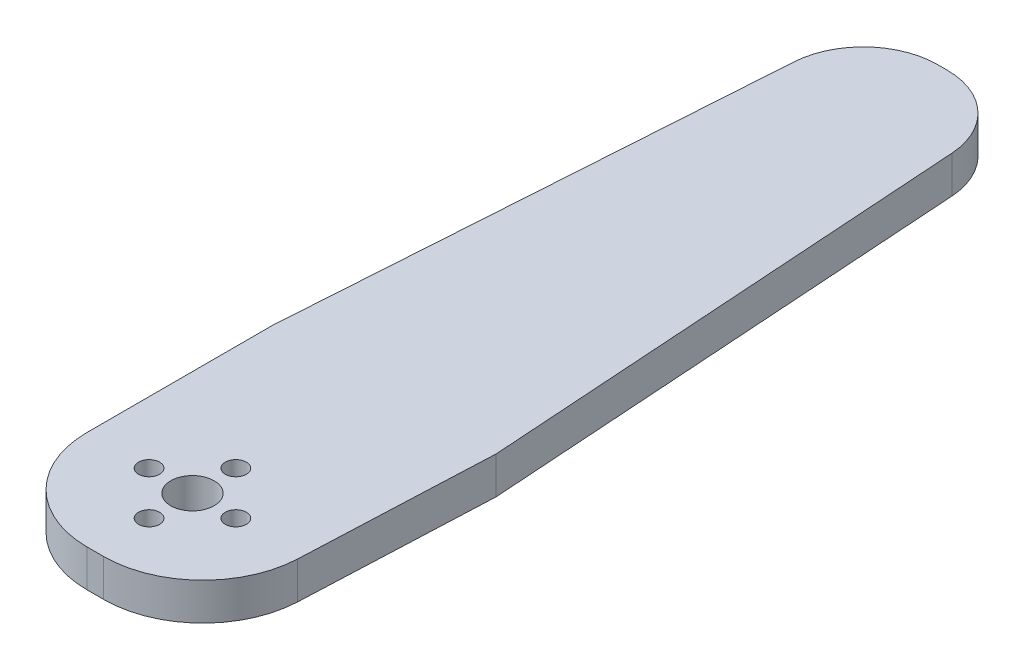
SolidWorks part; units mm, degrees
ref_plane "Front Plane" through (0, 0, 0) normal (0, 0, 1) x (1, 0, 0)
ref_plane "Top Plane" through (0, 0, 0) normal (0, 1, 0) x (1, 0, 0)
ref_plane "Right Plane" through (0, 0, 0) normal (1, 0, 0) x (0, 0, -1)
ref_plane "PY_m6_000" through (0, -6, 0) normal (0, 1, 0) x (1, 0, 0)
sketch "S_prism1" plane through (0, -6, 0) normal (0, 1, 0) x (1, 0, 0)
  line L0 (-1, -16) -> (1.6805, -16)
  line L1 (17.6654, -0.695) -> (19, 30)
  line L2 (19, 30) -> (13.7468, 108.7982)
  line L3 (1.7734, 120) -> (0.2266, 120)
  line L4 (-11.7468, 108.7982) -> (-17, 30)
  line L5 (-17, 30) -> (-17, 0)
  arc A0 (-17, 0) -> (-1, -16) centre (-1, 0) ccw
  arc A1 (1.6805, -16) -> (17.6654, -0.695) centre (1.6805, 0) ccw
  arc A2 (13.7468, 108.7982) -> (1.7734, 120) centre (1.7735, 108.0001) ccw
  arc A3 (0.2266, 120) -> (-11.7468, 108.7982) centre (0.2265, 108.0001) ccw
extrude "Boss_1" add sketch "S_prism1" along normal blind 6
ref_plane "PY_m8_000" through (0, -8, 0) normal (0, 1, 0) x (1, 0, 0)
sketch "S_cyl2" plane through (0, -8, 0) normal (0, 1, 0) x (1, 0, 0)
  circle A0 centre (0, 0) radius 12.5
  dimension "D1_S_cyl2" = 25
extrude "Boss_2" add sketch "S_cyl2" along normal blind 2
ref_plane "PY_m8_100" through (0, -8.1, 0) normal (0, 1, 0) x (1, 0, 0)
sketch "S_hole3" plane through (0, -8.1, 0) normal (0, 1, 0) x (1, 0, 0)
  circle A0 centre (0, 0) radius 3.5
  dimension "D1_S_hole3" = 7
extrude "Hole_3" cut sketch "S_hole3" along normal blind 8.2
sketch "S_hole4" plane through (0, -8.1, 0) normal (0, 1, 0) x (1, 0, 0)
  circle A0 centre (7, 0) radius 1.7
  dimension "D1_S_hole4" = 3.4
  dimension "P2" = 7
extrude "Hole_4" cut sketch "S_hole4" along normal blind 8.2
sketch "S_hole5" plane through (0, -8.1, 0) normal (0, 1, 0) x (1, 0, 0)
  circle A0 centre (0, -7) radius 1.7
  dimension "D1_S_hole5" = 3.4
  dimension "P2" = 7
extrude "Hole_5" cut sketch "S_hole5" along normal blind 8.2
sketch "S_hole6" plane through (0, -8.1, 0) normal (0, 1, 0) x (1, 0, 0)
  circle A0 centre (-7, 0) radius 1.7
  dimension "D1_S_hole6" = 3.4
  dimension "P2" = 7
extrude "Hole_6" cut sketch "S_hole6" along normal blind 8.2
sketch "S_hole7" plane through (0, -8.1, 0) normal (0, 1, 0) x (1, 0, 0)
  circle A0 centre (0, 7) radius 1.7
  dimension "D1_S_hole7" = 3.4
  dimension "P2" = 7
extrude "Hole_7" cut sketch "S_hole7" along normal blind 8.2
sketch "S_hole8" plane through (0, -8.1, 0) normal (0, 1, 0) x (1, 0, 0)
  circle A0 centre (7, 0) radius 3.2
  dimension "D1_S_hole8" = 6.4
  dimension "P2" = 7
extrude "Hole_8" cut sketch "S_hole8" along normal blind 5.1
sketch "S_hole9" plane through (0, -8.1, 0) normal (0, 1, 0) x (1, 0, 0)
  circle A0 centre (0, -7) radius 3.2
  dimension "D1_S_hole9" = 6.4
  dimension "P2" = 7
extrude "Hole_9" cut sketch "S_hole9" along normal blind 5.1
sketch "S_hole10" plane through (0, -8.1, 0) normal (0, 1, 0) x (1, 0, 0)
  circle A0 centre (-7, 0) radius 3.2
  dimension "D1_S_hole10" = 6.4
  dimension "P2" = 7
extrude "Hole_10" cut sketch "S_hole10" along normal blind 5.1
sketch "S_hole11" plane through (0, -8.1, 0) normal (0, 1, 0) x (1, 0, 0)
  circle A0 centre (0, 7) radius 3.2
  dimension "D1_S_hole11" = 6.4
  dimension "P2" = 7
extrude "Hole_11" cut sketch "S_hole11" along normal blind 5.1
equation "\"plate_t\" = 3"
equation "\"clearance\" = 0.5"
